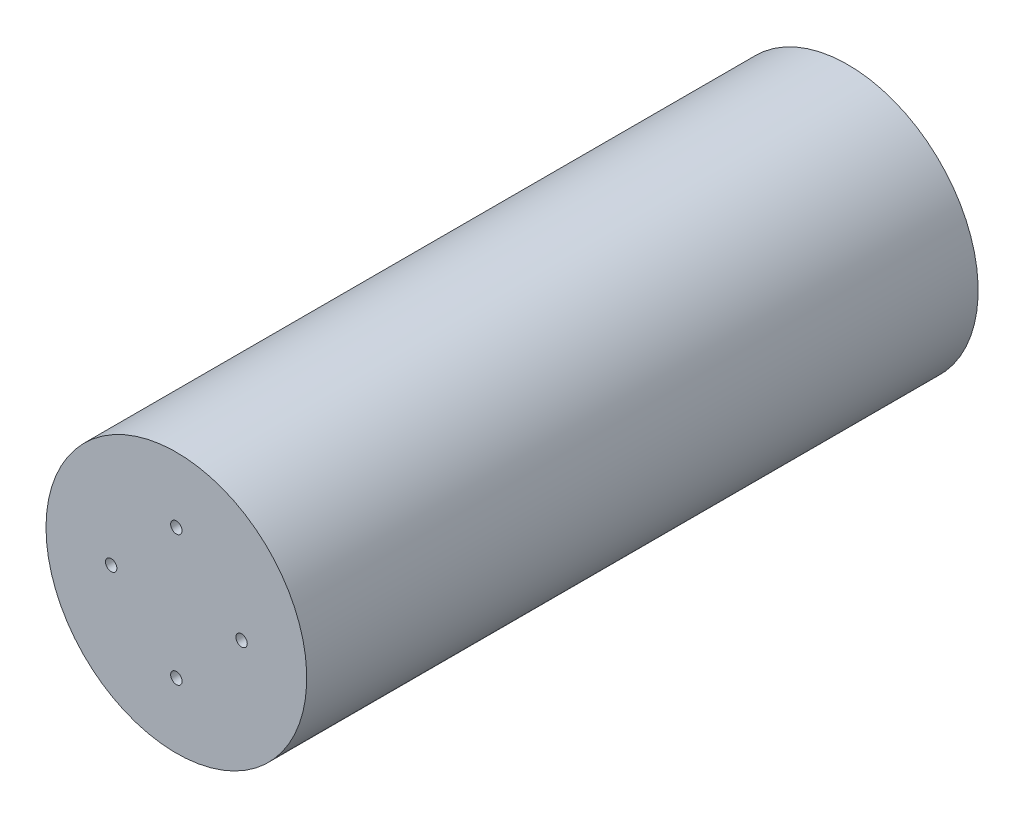
SolidWorks part; units mm, degrees
ref_plane "Alzado" through (0, 0, 0) normal (0, 0, 1) x (1, 0, 0)
ref_plane "Planta" through (0, 0, 0) normal (0, 1, 0) x (1, 0, 0)
ref_plane "Vista lateral" through (0, 0, 0) normal (1, 0, 0) x (0, 0, -1)
sketch "Croquis1" plane through (0, 0, 0) normal (0, 0, 1) x (1, 0, 0)
  line L1 (-117.2917, 97.7627) -> (131.4683, 97.7627)
  line L2 (-117.2917, 97.7627) -> (-117.2917, -97.2373)
  line L3 (-117.2917, -97.2373) -> (131.4683, -97.2373)
  line L4 (131.4683, 97.7627) -> (131.4683, -97.2373)
  dimension "D1" = 248.76
  dimension "D2" = 195
extrude "Saliente-Extruir1" add sketch "Croquis1" along normal blind 5
sketch "Croquis2" plane through (0, 0, 5) normal (0, 0, 1) x (1, 0, 0)
  line L0 (-117.2917, 0.2627) -> (131.4683, 0.2627) construction
  line L1 (-117.2917, 97.7627) -> (-117.2917, -97.2373) construction
  line L2 (131.4683, -97.2373) -> (131.4683, 97.7627) construction
  line L3 (-117.2917, -97.2373) -> (-69.2917, -97.2373)
  line L4 (-117.2917, -97.2373) -> (131.4683, -97.2373) construction
  line L5 (-69.2917, -97.2373) -> (-69.2917, -67.2373)
  line L6 (-69.2917, -67.2373) -> (-117.2917, -67.2373)
  line L7 (-117.2917, -67.2373) -> (-117.2917, -97.2373)
  line L8 (131.4683, 67.7627) -> (101.4683, 67.7627)
  line L9 (131.4683, -97.2373) -> (101.4683, -97.2373)
  line L10 (131.4683, -97.2373) -> (131.4683, -67.2373)
  line L11 (131.4683, -67.2373) -> (101.4683, -67.2373)
  line L12 (101.4683, -97.2373) -> (101.4683, -67.2373)
  line L13 (101.4683, 97.7627) -> (101.4683, 67.7627)
  line L14 (131.4683, 97.7627) -> (101.4683, 97.7627)
  line L15 (131.4683, 97.7627) -> (131.4683, 67.7627)
  line L16 (-69.2917, 67.7627) -> (-117.2917, 67.7627)
  line L17 (-69.2917, 97.7627) -> (-69.2917, 67.7627)
  line L18 (-117.2917, 97.7627) -> (-69.2917, 97.7627)
  line L19 (-117.2917, 67.7627) -> (-117.2917, 97.7627)
  dimension "D1" = 48
  dimension "D2" = 30
  dimension "D3" = 30
  dimension "D4" = 30
extrude "Cortar-Extruir1" cut sketch "Croquis2" against normal blind 2
sketch "Croquis3" plane through (0, 0, 5) normal (0, 0, 1) x (1, 0, 0)
  line L0 (-69.2917, 97.7627) -> (-117.2917, 97.7627) construction
  line L1 (116.4683, 83.7627) -> (116.4683, 67.7627) construction
  line L3 (116.4683, -83.2373) -> (116.4683, -67.2373) construction
  line L5 (131.4683, -67.2373) -> (101.4683, -67.2373) construction
  line L6 (101.4683, 67.7627) -> (131.4683, 67.7627) construction
  line L7 (-93.2917, 83.7627) -> (-93.2917, 67.7627) construction
  line L8 (-117.2917, 67.7627) -> (-69.2917, 67.7627) construction
  line L9 (-93.2917, -83.2373) -> (-93.2917, -67.2373) construction
  line L10 (-69.2917, -67.2373) -> (-117.2917, -67.2373) construction
  circle A0 centre (-93.2917, 83.7627) radius 2.375
  circle A1 centre (-93.2917, -83.2373) radius 2.375
  circle A2 centre (116.4683, 83.7627) radius 2.375
  circle A3 centre (116.4683, -83.2373) radius 2.375
  dimension "D2" = 4.75
  dimension "D3" = 4.75
  dimension "D5" = 4.75
  dimension "D6" = 4.75
  dimension "D1" = 14
  dimension "D4" = 14
  dimension "D7" = 209.76
  dimension "D8" = 16
  dimension "D9" = 16
extrude "Cortar-Extruir2" cut sketch "Croquis3" against normal blind 10
sketch "Croquis4" plane through (0, 0, 0) normal (0, 0, -1) x (-1, 0, 0)
  line L7 (-131.4683, 97.7627) -> (117.2917, 97.7627) construction
  line L9 (117.2917, 97.7627) -> (117.2917, -97.2373) construction
  circle A0 centre (55.1017, 0.2627) radius 40
  dimension "D3" = 80
  dimension "D1" = 62.19
  dimension "D2" = 97.5
extrude "Saliente-Extruir2" add sketch "Croquis4" along normal blind 206 contours A0
sketch "Croquis5" plane through (0, 0, 0) normal (0, 0, -1) x (-1, 0, 0)
  line L0 (-131.4683, 0.2627) -> (117.2917, 0.2627) construction
  line L1 (-131.4683, -97.2373) -> (-131.4683, 97.7627) construction
  line L2 (117.2917, 97.7627) -> (117.2917, -97.2373) construction
  circle A0 centre (-76.9683, 0.2627) radius 12.5
  dimension "D1" = 25
  dimension "D2" = 54.5
extrude "Cortar-Extruir3" cut sketch "Croquis5" against normal blind 10
sketch "Croquis6" plane through (0, 0, 0) normal (0, 0, -1) x (-1, 0, 0)
  line L0 (-131.4683, 97.7627) -> (117.2917, 97.7627) construction
  line L1 (-7.0883, 97.7627) -> (-7.0883, -97.2373)
  line L2 (117.2917, -97.2373) -> (-131.4683, -97.2373) construction
  line L3 (-7.0883, 97.7627) -> (117.2917, 97.7627)
  line L4 (117.2917, 97.7627) -> (117.2917, -97.2373)
  line L5 (117.2917, -97.2373) -> (-7.0883, -97.2373)
  line L6 (-131.4683, 0.2627) -> (56.0317, 0.2627)
  line L7 (-131.4683, -97.2373) -> (-131.4683, 97.7627) construction
  circle A1 centre (56.0317, 0.2627) radius 100
  dimension "D1" = 200
  dimension "D2" = 187.5
sketch "Croquis9" plane through (0, 97.7627, 0) normal (0, 1, 0) x (1, 0, 0)
  line L0 (7.0883, 0) -> (7.0883, -5)
  line L1 (131.4683, 0) -> (-117.2917, 0) construction
  line L2 (101.4683, -5) -> (-69.2917, -5) construction
ref_plane "Plano3" through (7.0883, 0, 0) normal (1, 0, 0) x (0, 0, -1)
sketch "Croquis12" plane through (7.0883, 0, 0) normal (1, 0, 0) x (0, 0, -1)
  line L0 (0, 97.7627) -> (0, 67.7627)
  line L1 (0, 67.7627) -> (12, 67.7627)
  line L2 (12, 67.7627) -> (12, 97.7627)
  line L3 (12, 97.7627) -> (0, 97.7627)
  line L4 (0, -97.2373) -> (12, -97.2373)
  line L5 (12, -97.2373) -> (12, -67.2373)
  line L6 (12, -67.2373) -> (0, -67.2373)
  line L7 (0, -67.2373) -> (0, -97.2373)
  dimension "D1" = 30
  dimension "D2" = 12
  dimension "D3" = 30
  dimension "D4" = 12
extrude "Saliente-Extruir3" add sketch "Croquis12" along normal mid plane 8
fillet "Redondeo1" radius 10 2 edges at (7.0883, -67.2373, 0) (7.0883, 67.7627, 0)
fillet "Redondeo2" radius 10 2 edges at (7.0883, 67.7627, -12) (7.0883, -67.2373, -12)
fillet "Redondeo3" radius 10 2 edges at (7.0883, -97.2373, -12) (7.0883, 97.7627, -12)
sketch "Croquis13" plane through (11.0883, 0, 0) normal (1, 0, 0) x (0, 0, -1)
  line L0 (-5, 0.2627) -> (206, 0.2627) construction
  line L1 (-5, -67.2373) -> (-5, 67.7627) construction
  line L2 (206, -39.7373) -> (206, 40.2627) construction
  line L3 (6, 87.7627) -> (12, 87.7627) construction
  line L4 (6, 87.7627) -> (6, 77.7627) construction
  circle A0 centre (6, 87.7627) radius 1.625
  circle A1 centre (6, 77.7627) radius 1.625
  circle A2 centre (6, -77.2373) radius 1.625
  circle A3 centre (6, -87.2373) radius 1.625
  dimension "D3" = 3.25
  dimension "D4" = 3.25
  dimension "D1" = 6
extrude "Cortar-Extruir5" cut sketch "Croquis13" against normal through all both and the other way through all
sketch "Croquis14" plane through (0, 0, 0) normal (0, 0, -1) x (-1, 0, 0)
  line L0 (-7.0883, 97.7627) -> (-7.0883, -97.2373)
  line L1 (-7.0883, 97.7627) -> (117.2917, 97.7627)
  line L2 (117.2917, 97.7627) -> (117.2917, -97.2373)
  line L3 (117.2917, -97.2373) -> (-7.0883, -97.2373)
sketch "Croquis15" plane through (0, 0, 5) normal (0, 0, 1) x (1, 0, 0)
  line L0 (111.4683, 67.7627) -> (131.4683, 67.7627)
  line L1 (111.4683, 67.7627) -> (111.4683, 60.0127)
  line L2 (131.4683, -67.2373) -> (101.4683, -67.2373) construction
  line L3 (111.4683, -67.2373) -> (111.4683, -59.4873)
  line L4 (111.4683, -59.4873) -> (125.2183, -59.4873)
  line L5 (125.2183, -59.4873) -> (125.2183, 60.0127)
  line L6 (111.4683, 60.0127) -> (125.2183, 60.0127)
  line L7 (111.4683, -67.2373) -> (131.4683, -67.2373)
  line L10 (131.4683, -67.2373) -> (131.4683, 67.7627)
  dimension "D1" = 119.5
  dimension "D2" = 7.75
  dimension "D3" = 13.75
extrude "Cortar-Extruir7" cut sketch "Croquis15" against normal blind 2
sketch "Croquis16" plane through (0, 0, 5) normal (0, 0, 1) x (1, 0, 0)
  circle A1 centre (-55.1017, 20.2627) radius 1.75
  circle A2 centre (-35.1017, 0.2627) radius 1.75
  circle A3 centre (-55.1017, -19.7373) radius 1.75
  circle A4 centre (-75.1017, 0.2627) radius 1.75
  dimension "D3" = 3.5
  dimension "D4" = 4
extrude "Cortar-Extruir9" cut sketch "Croquis16" against normal blind 20
sketch "Croquis20" plane through (0, -97.2373, 0) normal (0, -1, 0) x (1, 0, 0)
  line L0 (-117.2917, 10.5315) -> (-117.2917, 0)
  line L1 (-117.2917, 0) -> (3.0883, 0)
  line L2 (3.0883, 0) -> (3.0883, -12)
  line L3 (3.0883, -12) -> (11.0883, -12)
  line L4 (11.0883, -12) -> (11.0883, 0)
  line L5 (11.0883, 0) -> (131.4683, 0)
  line L6 (131.4683, 0) -> (131.4683, 10.5315)
  line L7 (131.4683, 10.5315) -> (-117.2917, 10.5315)
extrude "Cortar-Extruir17" cut sketch "Croquis20" against normal through all both and the other way through all
